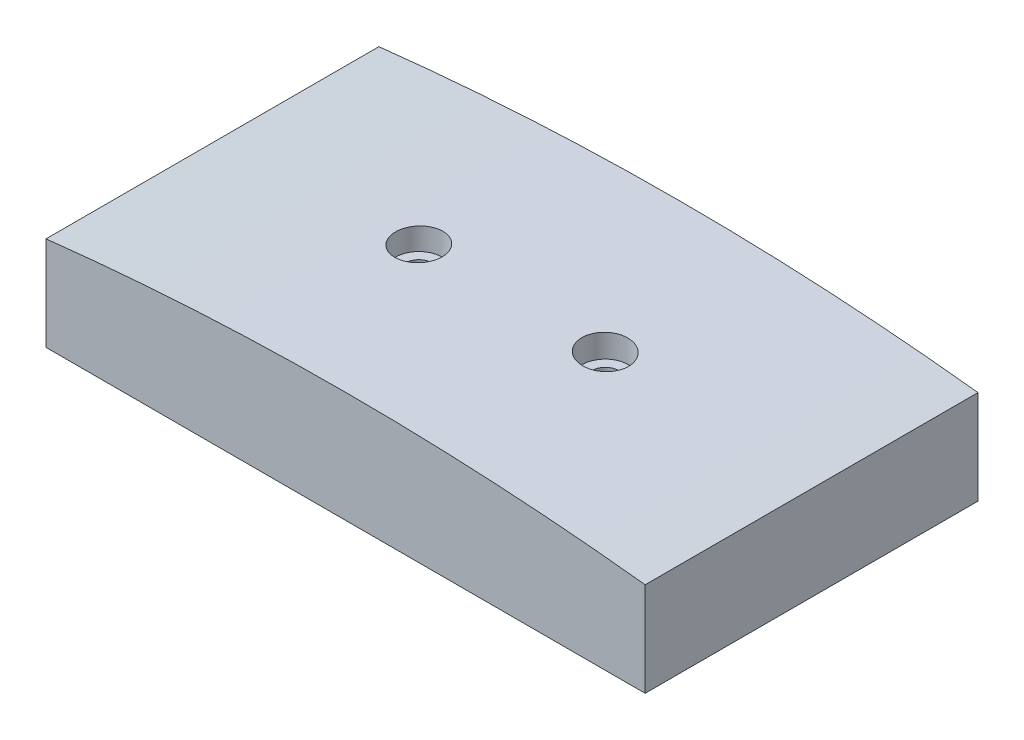
SolidWorks part; units mm, degrees
ref_plane "Front Plane" through (0, 0, 0) normal (0, 0, 1) x (1, 0, 0)
ref_plane "Top Plane" through (0, 0, 0) normal (0, 1, 0) x (1, 0, 0)
ref_plane "Right Plane" through (0, 0, 0) normal (1, 0, 0) x (0, 0, -1)
sketch "Sketch1" plane through (0, 0, 0) normal (0, 0, 1) x (1, 0, 0)
  line L0 (0, 0) -> (0, 17) construction
  line L2 (-45, 14.1225) -> (-45, 0)
  line L3 (-45, 0) -> (45, 0)
  line L4 (45, 14.1225) -> (45, 0)
  line L5 (-45, 17) -> (45, 0) construction
  line L6 (-45, 0) -> (45, 17) construction
  arc A0 (-45, 14.1225) -> (45, 14.1225) centre (0, -383.3382) cw
  point P0 (0, 8.5)
  point P9 (0, 0)
  point P12 (0, 0)
  dimension "D5" = 400
  dimension "D1" = 17
  dimension "D2" = 90
extrude "Boss-Extrude1" add sketch "Sketch1" along normal mid plane 50
sketch "Sketch2" plane through (0, 0, 0) normal (0, -1, 0) x (1, 0, 0)
  line L0 (0, 0) -> (0, 25) construction
  line L1 (-45, 25) -> (45, 25) construction
  circle A0 centre (-14, 0) radius 3.5
  circle A1 centre (14, 0) radius 3.5
  point P7 (0, 0)
  dimension "D1" = 7
  dimension "D2" = 28
extrude "Cut-Extrude2" cut sketch "Sketch2" along normal blind 5 from offset 18 offset against normal yes
sketch "Sketch4" plane through (0, 13, 0) normal (0, 1, 0) x (1, 0, 0)
  circle A0 centre (-14, 0) radius 2
  point P3 (0, 0)
  dimension "D1" = 4
extrude "Cut-Extrude3" cut sketch "Sketch4" against normal through all
mirror "Mirror2" about plane through (0, 0, 0) normal (1, 0, 0) of "Cut-Extrude3"
